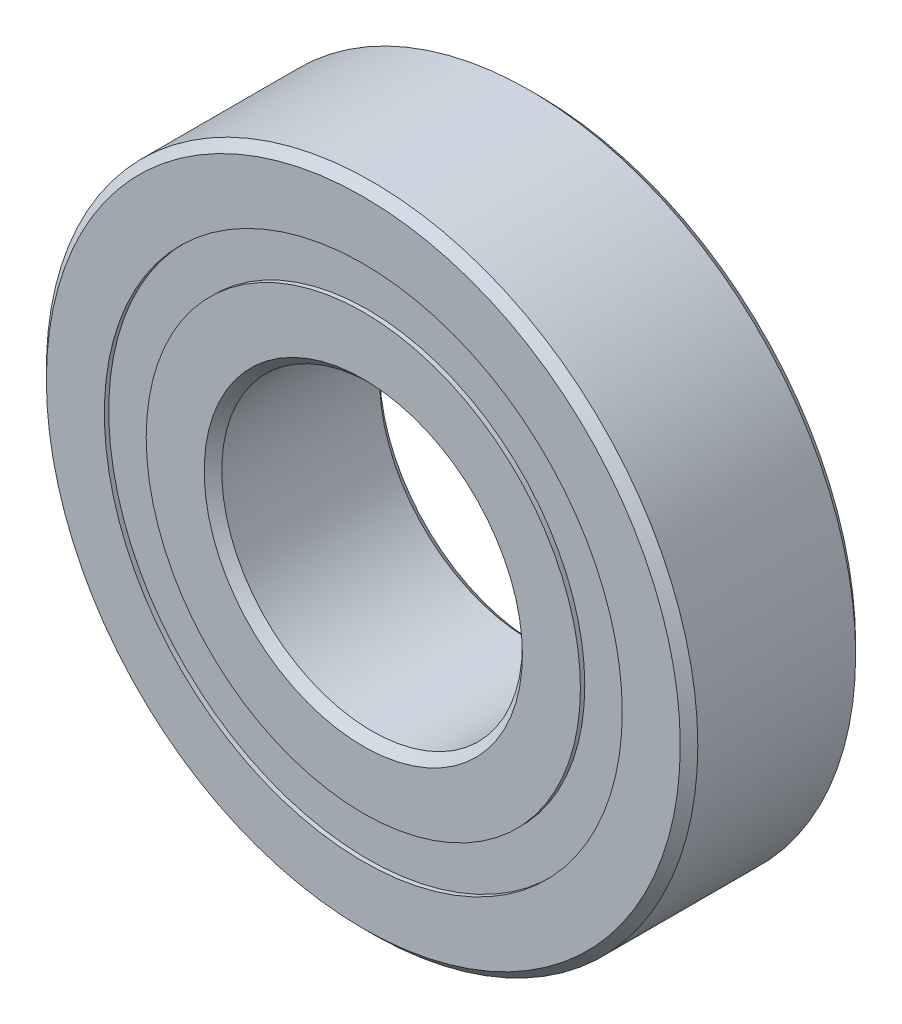
SolidWorks part; units mm, degrees
ref_plane "Front Plane" through (0, 0, 0) normal (0, 0, 1) x (1, 0, 0)
ref_plane "Top Plane" through (0, 0, 0) normal (0, 1, 0) x (1, 0, 0)
ref_plane "Right Plane" through (0, 0, 0) normal (1, 0, 0) x (0, 0, -1)
sketch "Sketch1" plane through (0, 0, 0) normal (1, 0, 0) x (0, 0, -1)
  line L0 (-5.5562, 0) -> (5.5562, 0) construction
  line L1 (0, 20.6375) -> (0, -20.6375) construction
  line L2 (5.0006, 20.6375) -> (-5.0006, 20.6375)
  line L3 (-5.0006, 20.6375) -> (-5.5563, 20.0819)
  line L4 (-5.5563, 20.0819) -> (-5.5563, 16.4071)
  line L5 (-5.5563, 16.4071) -> (-2.4694, 16.4071)
  line L6 (5.5563, 16.4071) -> (2.4694, 16.4071)
  line L7 (5.5563, 20.0819) -> (5.5563, 16.4071)
  line L8 (5.0006, 20.6375) -> (5.5563, 20.0819)
  line L9 (0, 20.6375) -> (0, 15.0813) construction
  line L10 (0, 15.0813) -> (0, 9.525) construction
  arc A0 (-2.4694, 16.4071) -> (2.4694, 16.4071) centre (0, 15.0813) cw
  point P14 (0, 9.525)
  dimension "D3" = 4.9389
  dimension "D1" = 45
  dimension "Width" = 11.1125
  dimension "OD" = 41.275
  dimension "D2" = 0.5556
  dimension "Shaft Dia" = 19.05
  dimension "D4" = 1.3258
revolve "Revolve1" add sketch "Sketch1" angle 360 about L0
sketch "Sketch3" plane through (0, 0, 0) normal (1, 0, 0) x (0, 0, -1)
  line L0 (-5.5563, 13.7554) -> (-2.4694, 13.7554)
  line L1 (0, 20.6375) -> (0, -20.6375) construction
  line L2 (-5.5563, 20.0819) -> (-5.5563, 16.4071) construction
  line L3 (-5.5563, 13.7554) -> (-5.5563, 10.0806)
  line L4 (-5.0006, 20.6375) -> (-5.5563, 20.0819) construction
  line L5 (-5.5563, 10.0806) -> (-5.0006, 9.525)
  line L6 (-5.0006, 9.525) -> (5.0006, 9.525)
  line L7 (5.0006, 20.6375) -> (5.0006, -20.6375) construction
  line L8 (5.0006, 9.525) -> (5.5563, 10.0806)
  line L9 (5.5563, -20.0819) -> (5.5563, 20.0819) construction
  line L10 (5.5563, 10.0806) -> (5.5563, 13.7554)
  line L11 (5.5563, 13.7554) -> (2.4694, 13.7554)
  line L13 (5.0006, 20.6375) -> (5.5563, 20.0819) construction
  arc A0 (2.4694, 16.4071) -> (-2.4694, 16.4071) centre (0, 15.0813) ccw construction
  arc A1 (2.4694, 13.7554) -> (-2.4694, 13.7554) centre (0, 15.0812) cw
revolve "Revolve3" add sketch "Sketch3" angle 360 about L0
sketch "Sketch4" plane through (0, 0, 0) normal (1, 0, 0) x (0, 0, -1)
  line L0 (-2.8028, 15.0813) -> (2.8028, 15.0813)
  arc A2 (-2.8028, 15.0813) -> (2.8028, 15.0813) centre (0, 15.0813) cw
  arc A3 (2.4694, 16.4071) -> (-2.4694, 16.4071) centre (0, 15.0813) ccw construction
revolve "Revolve4" add sketch "Sketch4" angle 360 about L0
ref_axis "Axis1" through (0, 0, -5.5562) along (0, 0, 1)
pattern_circular "CirPattern1" count 12 every 30 about axis through (0, 0, -5.5562) along (0, 0, 1) of bodies 104
sketch "Sketch5" plane through (0, 0, 0) normal (1, 0, 0) x (0, 0, -1)
  line L0 (-5.5563, 16.4071) -> (-2.4694, 16.4071) construction
  line L1 (-5.2784, 16.4071) -> (-2.8028, 16.4071)
  line L2 (-5.2784, 16.4071) -> (-5.2784, 13.7554)
  line L3 (-5.2784, 13.7554) -> (-2.8028, 13.7554)
  line L4 (-2.8028, 16.4071) -> (-2.8028, 13.7554)
  line L5 (-5.5563, 13.7554) -> (-2.4694, 13.7554) construction
  line L6 (5.5563, 16.4071) -> (2.4694, 16.4071) construction
  line L7 (5.2784, 16.4071) -> (2.8028, 16.4071)
  line L8 (5.2784, 16.4071) -> (5.2784, 13.7554)
  line L9 (5.2784, 13.7554) -> (2.8028, 13.7554)
  line L10 (2.8028, 16.4071) -> (2.8028, 13.7554)
  line L11 (5.5563, 13.7554) -> (2.4694, 13.7554) construction
  line L12 (-5.0006, 20.6375) -> (-5.5563, 20.0819) construction
  point P18 (-5.2784, 20.3597)
revolve "Revolve5" add sketch "Sketch5" angle 360 about L0
equation "\"D2@Sketch1\" = \"Width@Sketch1\"*.05"
equation "\"D3@Sketch1\" = \"Width@Sketch1\"/2.25"
equation "\"D4@Sketch1\" = (((\"OD@Sketch1\"-\"Width@Sketch1\")/2)/3.25)/3.5"
equation "\"D2@CirPattern1\" = 360/\"Balls@CirPattern1\""
